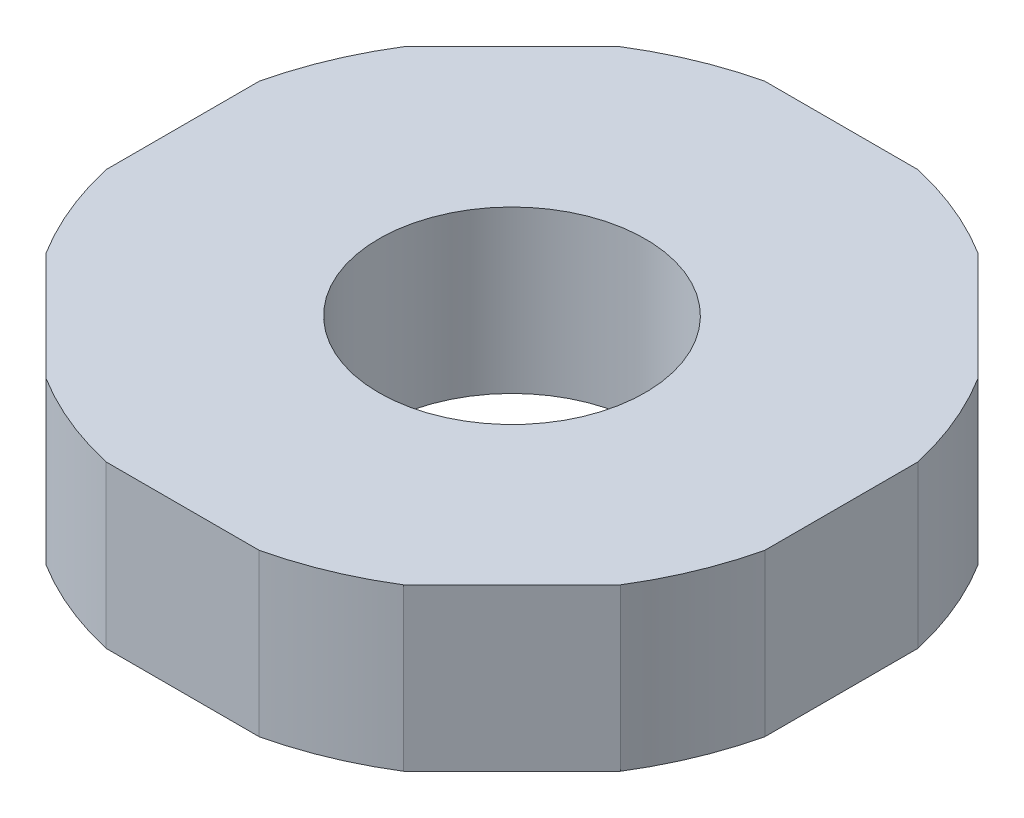
SolidWorks part; units mm, degrees
ref_plane "Front Plane" through (0, 0, 0) normal (0, 0, 1) x (1, 0, 0)
ref_plane "Top Plane" through (0, 0, 0) normal (0, 1, 0) x (1, 0, 0)
ref_plane "Right Plane" through (0, 0, 0) normal (1, 0, 0) x (0, 0, -1)
sketch "Sketch1" plane through (0, 0, 0) normal (0, 1, 0) x (1, 0, 0)
  line L8 (3.3208, -5.3361) -> (5.3361, -3.3208)
  line L9 (6.1213, -1.425) -> (6.1213, 1.425)
  line L10 (5.3361, 3.3208) -> (3.3208, 5.3361)
  line L11 (1.425, 6.1213) -> (-1.425, 6.1213)
  line L12 (-3.3208, 5.3361) -> (-5.3361, 3.3208)
  line L13 (-6.1213, 1.425) -> (-6.1213, -1.425)
  line L14 (-5.3361, -3.3208) -> (-3.3208, -5.3361)
  line L15 (-1.425, -6.1213) -> (1.425, -6.1213)
  line L16 (3.3208, -5.3361) -> (5.3361, -3.3208)
  line L17 (6.1213, -1.425) -> (6.1213, 1.425)
  line L18 (5.3361, 3.3208) -> (3.3208, 5.3361)
  line L19 (1.425, 6.1213) -> (-1.425, 6.1213)
  line L20 (-3.3208, 5.3361) -> (-5.3361, 3.3208)
  line L21 (-6.1213, 1.425) -> (-6.1213, -1.425)
  line L22 (-5.3361, -3.3208) -> (-3.3208, -5.3361)
  line L23 (-1.425, -6.1213) -> (1.425, -6.1213)
  circle A0 centre (0, 0) radius 2.475 construction
  circle A1 centre (0, 0) radius 2.475
  arc A8 (1.425, -6.1213) -> (3.3208, -5.3361) centre (0, 0) ccw
  arc A9 (5.3361, -3.3208) -> (6.1213, -1.425) centre (0, 0) ccw
  arc A10 (6.1213, 1.425) -> (5.3361, 3.3208) centre (0, 0) ccw
  arc A11 (3.3208, 5.3361) -> (1.425, 6.1213) centre (0, 0) ccw
  arc A12 (-1.425, 6.1213) -> (-3.3208, 5.3361) centre (0, 0) ccw
  arc A13 (-5.3361, 3.3208) -> (-6.1213, 1.425) centre (0, 0) ccw
  arc A14 (-6.1213, -1.425) -> (-5.3361, -3.3208) centre (0, 0) ccw
  arc A15 (-3.3208, -5.3361) -> (-1.425, -6.1213) centre (0, 0) ccw
  arc A16 (1.425, -6.1213) -> (3.3208, -5.3361) centre (0, 0) ccw
  arc A17 (5.3361, -3.3208) -> (6.1213, -1.425) centre (0, 0) ccw
  arc A18 (6.1213, 1.425) -> (5.3361, 3.3208) centre (0, 0) ccw
  arc A19 (3.3208, 5.3361) -> (1.425, 6.1213) centre (0, 0) ccw
  arc A20 (-1.425, 6.1213) -> (-3.3208, 5.3361) centre (0, 0) ccw
  arc A21 (-5.3361, 3.3208) -> (-6.1213, 1.425) centre (0, 0) ccw
  arc A22 (-6.1213, -1.425) -> (-5.3361, -3.3208) centre (0, 0) ccw
  arc A23 (-3.3208, -5.3361) -> (-1.425, -6.1213) centre (0, 0) ccw
  dimension "D1" = 0
extrude "Boss-Extrude1" add sketch "Sketch1" against normal blind 3
